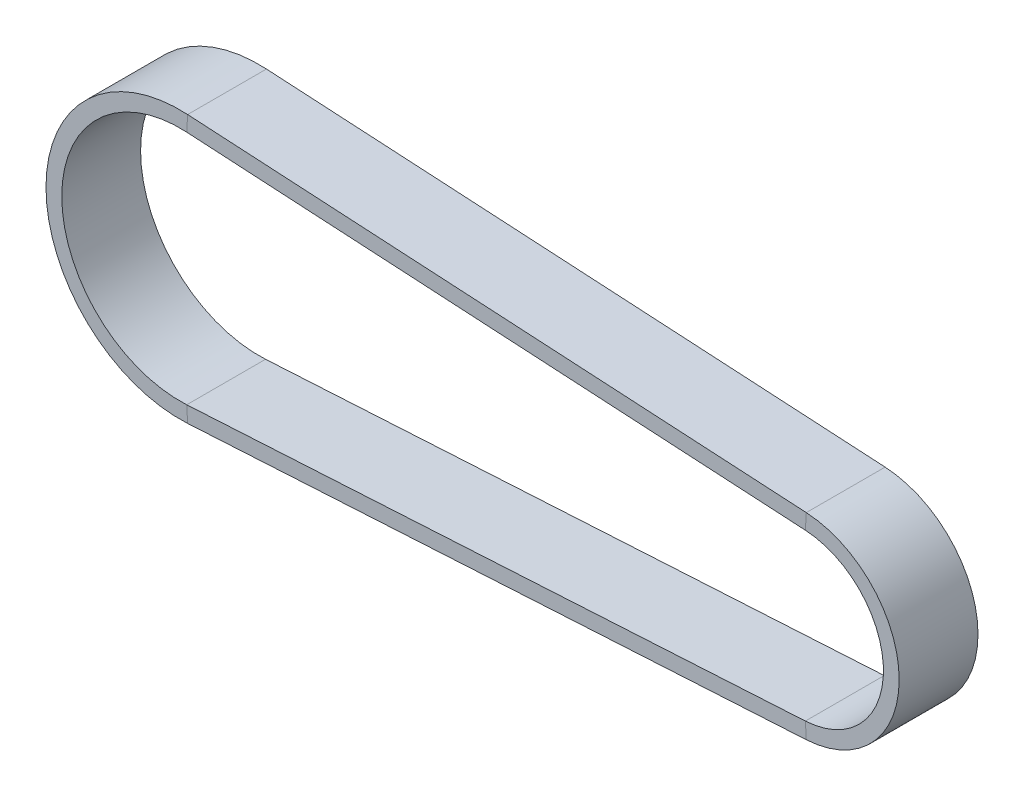
SolidWorks part; units mm, degrees
ref_plane "Ebene vorne" through (0, 0, 0) normal (0, 0, 1) x (1, 0, 0)
ref_plane "Ebene oben" through (0, 0, 0) normal (0, 1, 0) x (1, 0, 0)
ref_plane "Ebene rechts" through (0, 0, 0) normal (1, 0, 0) x (0, 0, -1)
sketch "Skizze2" plane through (0, 0, 0) normal (0, 1, 0) x (1, 0, 0)
  line L0 (-15, -20.5) -> (-17, -20.5) construction
  line L1 (-17, -10.5) -> (-17, -20.5) construction
  line L2 (-15, -10.5) -> (-17, -10.5) construction
  line L3 (-15, -10.5) -> (-15, -20.5) construction
  line L4 (-15, -20.5) -> (-17, -20.5)
  line L5 (-17, -10.5) -> (-17, -20.5)
  line L6 (-15, -10.5) -> (-17, -10.5)
  line L7 (-15, -10.5) -> (-15, -20.5)
ref_plane "Ebene1" through (0, 0, 15.5) normal (0, 0, 1) x (1, 0, 0)
sketch "Skizze3" plane through (0, 0, 15.5) normal (0, 0, 1) x (1, 0, 0)
  line L0 (0.8857, 15.4747) -> (79.3786, 10.982) construction
  line L1 (0.8857, 15.4747) -> (79.3786, 10.982)
  arc A0 (89.75, 0) -> (79.3786, 10.982) centre (78.75, 0) ccw construction
  arc A1 (0.8857, 15.4747) -> (-15.5, 0) centre (0, 0) ccw construction
  arc A2 (89.75, 0) -> (79.3786, 10.982) centre (78.75, 0) ccw
  arc A3 (0.8857, 15.4747) -> (-15.5, 0) centre (0, 0) ccw
sweep "Austragung1" add profiles "Skizze2" path "Skizze3"
mirror "Spiegeln1" about plane through (0, 0, 0) normal (0, -1, 0) of bodies 101
